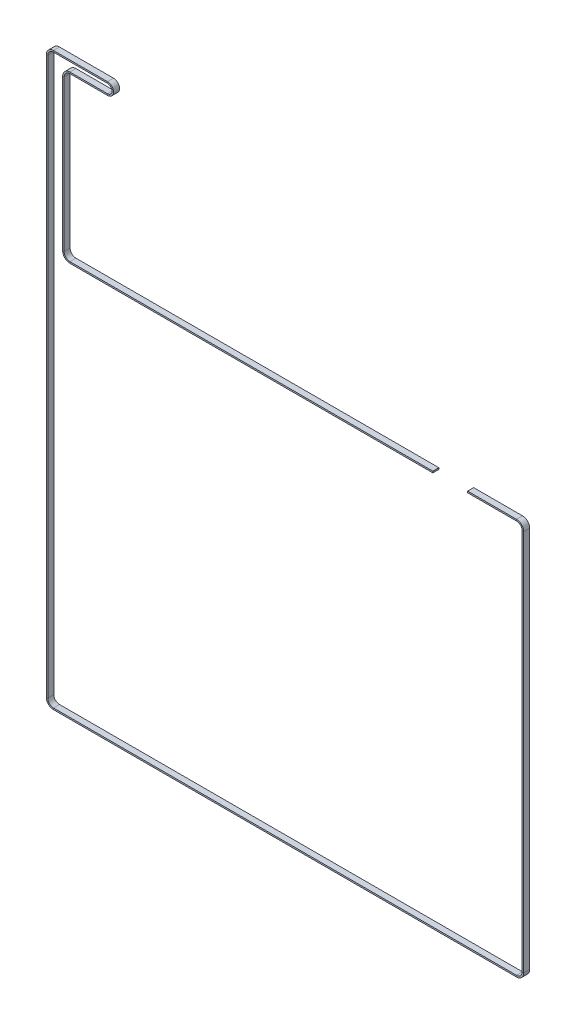
SolidWorks part; units mm, degrees
ref_plane "Front" through (0, 0, 0) normal (0, 0, 1) x (1, 0, 0)
ref_plane "Top" through (0, 0, 0) normal (0, 1, 0) x (1, 0, 0)
ref_plane "Right" through (0, 0, 0) normal (1, 0, 0) x (0, 0, -1)
sketch "Sketch1" plane through (0, -21, 4.45) normal (0, 0, 1) x (1, 0, 0)
  line L0 (10, 63.3) -> (47.5, 63.3)
  line L1 (47.5, 73.7) -> (-6.5, 73.7)
  line L2 (-12.875, 67.325) -> (-12.875, -488)
  line L3 (-6.5, -494.375) -> (455.5, -494.375)
  line L4 (461.875, -488) -> (461.875, -106.7716)
  line L5 (455.5, -100.3966) -> (406.7057, -100.3966)
  line L7 (3.4, 56.7) -> (3.4, -93.9466)
  line L8 (10, -100.5466) -> (372.0057, -100.5466)
  line L10 (372.0057, -100.4466) -> (372.0057, -103.9466) construction
  line L11 (406.7057, -99.5466) -> (406.7057, -92.9466) construction
  circle A0 centre (47.5, 68.5) radius 5.2 construction
  circle A1 centre (10, 56.7) radius 6.6 construction
  circle A2 centre (-6.5, 67.325) radius 6.375 construction
  circle A3 centre (10, -93.9466) radius 6.6 construction
  circle A4 centre (-6.5, -488) radius 6.375 construction
  circle A5 centre (455.5, -488) radius 6.375 construction
  circle A6 centre (455.5, -106.7716) radius 6.375 construction
  arc A7 (47.5, 73.7) -> (47.5, 63.3) centre (47.5, 68.5) cw
  arc A8 (10, 63.3) -> (3.4, 56.7) centre (10, 56.7) ccw
  arc A9 (-12.875, 67.325) -> (-6.5, 73.7) centre (-6.5, 67.325) cw
  arc A10 (-6.5, -494.375) -> (-12.875, -488) centre (-6.5, -488) cw
  arc A11 (455.5, -494.375) -> (461.875, -488) centre (455.5, -488) ccw
  arc A12 (461.875, -106.7716) -> (455.5, -100.3966) centre (455.5, -106.7716) ccw
  arc A13 (3.4, -93.9466) -> (10, -100.5466) centre (10, -93.9466) ccw
  circle A14 centre (-6.5, 67.325) radius 9 construction
  circle A15 centre (455.5, -106.7716) radius 5.9875 construction
  circle A16 centre (10, -93.9466) radius 5.9875 construction
  dimension "D1" = 12.75
ref_plane "Plane1" through (406.7057, -121.3966, 4.45) normal (-1, 0, 0) x (0, 0, 1)
sketch "Sketch2" plane through (406.7057, -121.3966, 4.45) normal (-1, 0, 0) x (0, 0, 1)
  line L1 (-3, 0.75) -> (3, 0.75)
  line L2 (-3, 0.75) -> (-3, -0.75)
  line L3 (-3, -0.75) -> (3, -0.75)
  line L4 (3, 0.75) -> (3, -0.75)
  line L5 (-3, 0.75) -> (3, -0.75) construction
  line L6 (-3, -0.75) -> (3, 0.75) construction
  point P0 (0, 0)
  dimension "D1" = 6
  dimension "D2" = 1.5
sweep "Sweep1" add profiles "Sketch2" path "Sketch1"
